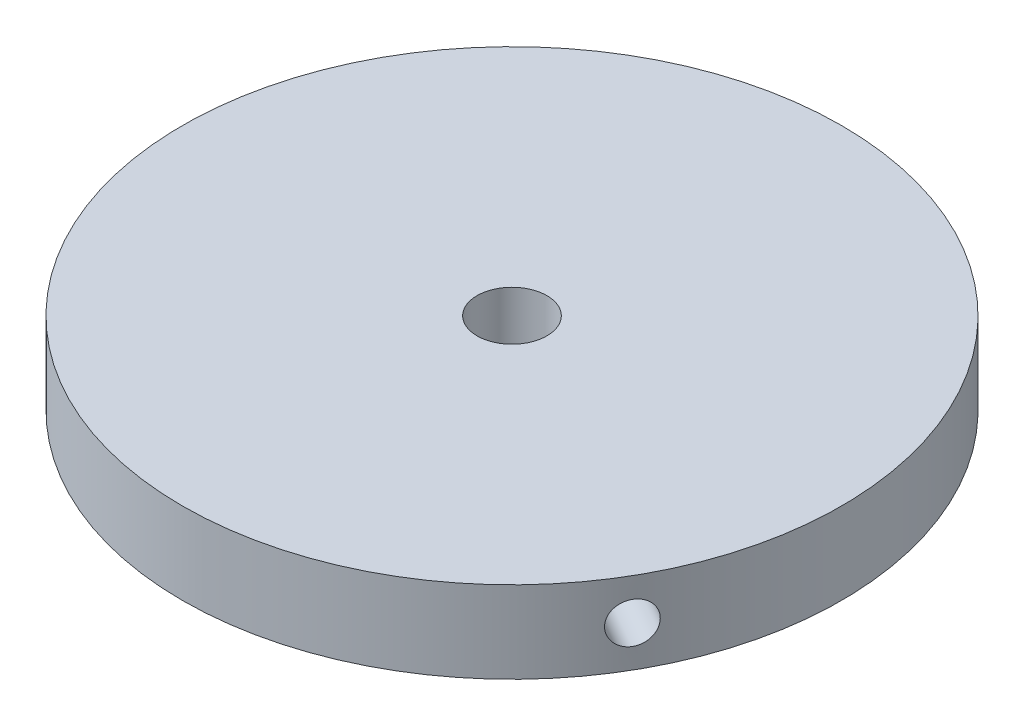
SolidWorks part; units mm, degrees
material "G10 Fiberglass"
ref_plane "Front Plane" through (0, 0, 0) normal (0, 0, 1) x (1, 0, 0)
ref_plane "Top Plane" through (0, 0, 0) normal (0, 1, 0) x (1, 0, 0)
ref_plane "Right Plane" through (0, 0, 0) normal (1, 0, 0) x (0, 0, -1)
sketch "Sketch1" plane through (0, 0, 0) normal (0, 1, 0) x (1, 0, 0)
  circle A0 centre (0, 0) radius 38.354
  dimension "D1" = 76.708
extrude "Boss-Extrude1" add sketch "Sketch1" along normal blind 9.525
ref_plane "Plane1" through (-33.2155, 0, 19.177) normal (-0.866, 0, 0.5) x (0, -1, 0)
sketch "Sketch4" plane through (-33.2155, 0, 19.177) normal (-0.866, 0, 0.5) x (0, -1, 0)
  circle A0 centre (-4.7625, 0) radius 2.3749
  dimension "D1" = 4.7625
  dimension "D2" = 4.7498
extrude "Cut-Extrude2" cut sketch "Sketch4" against normal blind 6.35
ref_axis "Axis1" through (0, 10.0012, 0) along (0, -1, 0)
pattern_circular "CirPattern1" count 3 over 360 about axis through (0, 10.0012, 0) along (0, -1, 0) of "Cut-Extrude2"
sketch "Sketch6" plane through (0, 9.525, 0) normal (0, 1, 0) x (1, 0, 0)
  circle A0 centre (0, 0) radius 4.064
  dimension "D1" = 8.128
extrude "Cut-Extrude4" cut sketch "Sketch6" against normal through all
